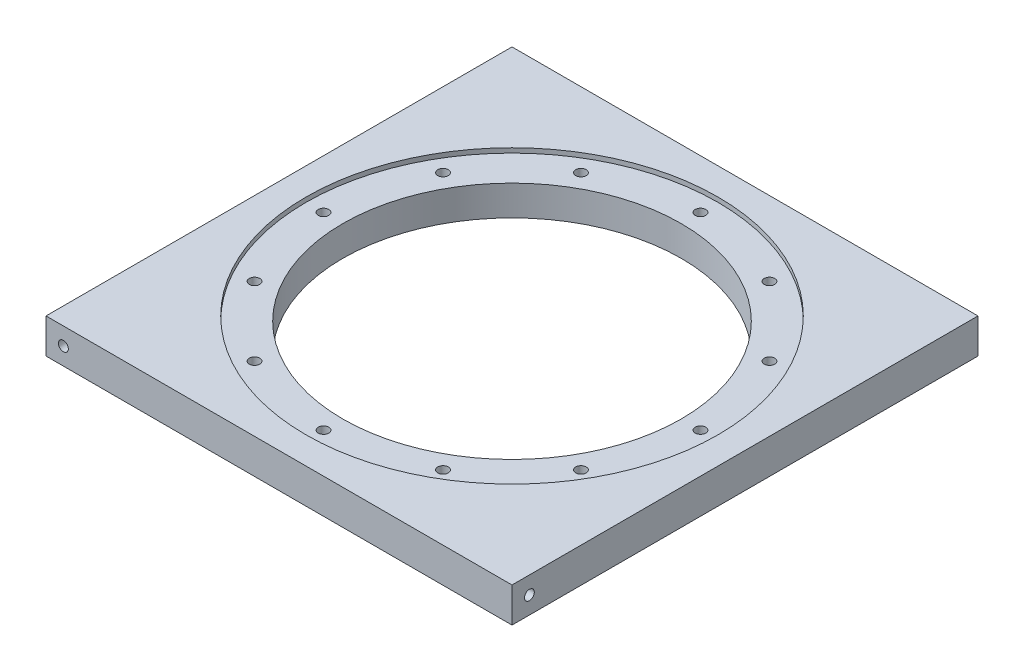
SolidWorks part; units mm, degrees
material "6061-T6 (SS)"
ref_plane "Front Plane" through (0, 0, 0) normal (0, 0, 1) x (1, 0, 0)
ref_plane "Top Plane" through (0, 0, 0) normal (0, 1, 0) x (1, 0, 0)
ref_plane "Right Plane" through (0, 0, 0) normal (1, 0, 0) x (0, 0, -1)
sketch "Sketch1" plane through (0, 0, 0) normal (0, 1, 0) x (1, 0, 0)
  line L5 (0, 0) -> (127.635, 0)
  line L6 (0, 0) -> (0, 127.635)
  line L7 (0, 127.635) -> (127.635, 127.635)
  line L8 (127.635, 0) -> (127.635, 127.635)
  dimension "D1" = 127.635
  dimension "D2" = 127.635
extrude "Boss-Extrude1" add sketch "Sketch1" along normal blind 9.525 contours L5 L8 L7 L6
sketch "Sketch6" plane through (127.635, 0, 0) normal (1, 0, 0) x (0, 0, -1)
  circle A0 centre (4.7625, 4.7625) radius 1.3526
  dimension "D1" = 2.7051
extrude "6-32 hole1" cut sketch "Sketch6" against normal blind 12.7
sketch "Sketch7" plane through (0, 0, -127.635) normal (0, 0, -1) x (-1, 0, 0)
  circle A0 centre (-122.8725, 4.7625) radius 1.3525
  dimension "D1" = 2.7051
extrude "6-32 hole2" cut sketch "Sketch7" against normal blind 12.7
sketch "Sketch8" plane through (0, 0, 0) normal (-1, 0, 0) x (0, 0, 1)
  circle A0 centre (-122.8725, 4.7625) radius 1.3525
  dimension "D1" = 2.7051
extrude "6-32 hole3" cut sketch "Sketch8" against normal blind 12.7
sketch "Sketch9" plane through (0, 0, 0) normal (0, 0, 1) x (1, 0, 0)
  circle A0 centre (4.7625, 4.7625) radius 1.3526
  dimension "D1" = 2.7051
extrude "6-32 hole4" cut sketch "Sketch9" against normal blind 12.7
sketch "Sketch5" plane through (0, 9.525, 0) normal (0, 1, 0) x (1, 0, 0)
  line L0 (63.8175, 0) -> (63.8175, 127.635) construction
  line L3 (0, 0) -> (127.635, 0) construction
  line L8 (0, 127.635) -> (127.635, 127.635) construction
  circle A0 centre (63.8175, 63.8175) radius 46.355
  dimension "D1" = 92.71
extrude "Cut-Extrude1" cut sketch "Sketch5" against normal blind 9.525 contours L0 A0 | A0 L0
sketch "Sketch11" plane through (0, 9.525, 0) normal (0, 1, 0) x (1, 0, 0)
  line L0 (63.8175, 63.8175) -> (63.8175, 115.443) construction
  circle A0 centre (63.8175, 115.443) radius 1.4351
  dimension "D2" = 2.8702
  dimension "D1" = 51.6255
extrude "Cut-Extrude3" cut sketch "Sketch11" against normal through all contours A0
pattern_circular "CirPattern1" count 12 over 360 about axis through (63.8175, 9.525, -63.8175) along (0, 1, 0) of "Cut-Extrude3"
sketch "Sketch12" plane through (0, 9.525, 0) normal (0, 1, 0) x (1, 0, 0)
  circle A0 centre (63.8175, 63.8175) radius 56.4198
  dimension "D1" = 112.8395
extrude "Cut-Extrude4" cut sketch "Sketch12" against normal blind 1.27
